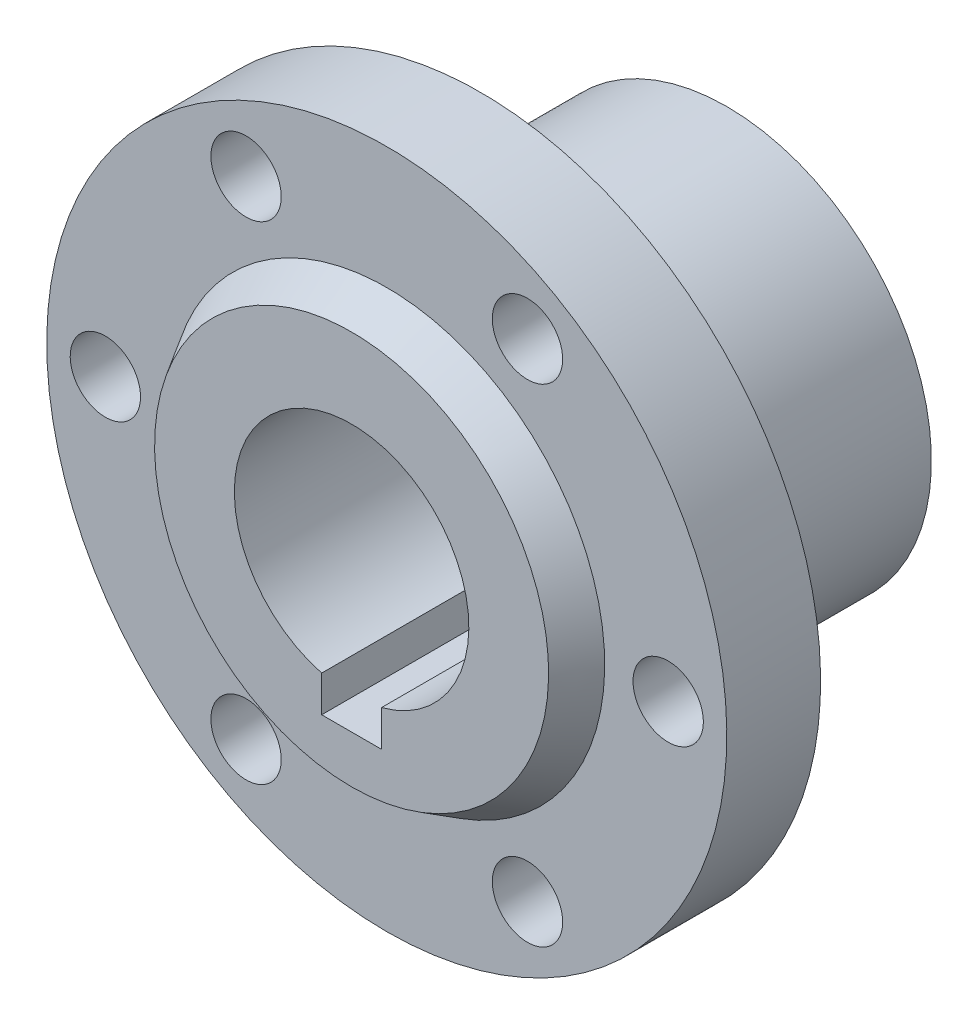
SolidWorks part; units mm, degrees
ref_plane "Front Plane" through (0, 0, 0) normal (0, 0, 1) x (1, 0, 0)
ref_plane "Top Plane" through (0, 0, 0) normal (0, 1, 0) x (1, 0, 0)
ref_plane "Right Plane" through (0, 0, 0) normal (1, 0, 0) x (0, 0, -1)
sketch "Sketch1" plane through (0, 0, 0) normal (1, 0, 0) x (0, 0, -1)
  line L0 (-11, 0) -> (21, 0) construction
  line L1 (21, 0) -> (21, 17.45) construction
  line L2 (21, 17.45) -> (7.03, 17.45)
  line L3 (7.03, 17.45) -> (7.03, 18.5)
  line L4 (7.03, 18.5) -> (0, 18.5)
  line L6 (0, 18.5) -> (0, 29)
  line L8 (0, 29) -> (-8, 29)
  line L9 (-8, 29) -> (-8, 18.5862)
  line L11 (-8, 18.5862) -> (-11, 16.8032)
  line L12 (-11, 16.8032) -> (-11, 0) construction
  line L13 (-11, 10) -> (21, 10)
  line L14 (-11, 10) -> (-11, 16.8032)
  line L15 (21, 10) -> (21, 17.45)
  point P22 (-11, 9.6803)
  dimension "D1" = 10
  dimension "D2" = 29
  dimension "D3" = 18.5
  dimension "D4" = 17.45
  dimension "D5" = 13.97
  dimension "D6" = 6.8032
  dimension "D7" = 8
revolve "Revolve1" add sketch "Sketch1" angle 360 about L0
sketch "Sketch2" plane through (0, 0, 0) normal (0, 0, 1) x (1, 0, 0)
  line L0 (0, 0) -> (0, -12.75) construction
  line L1 (-2.55, -12.75) -> (2.55, -12.75)
  line L2 (-2.55, -12.75) -> (-2.55, -9.6694)
  line L3 (2.55, -12.75) -> (2.55, -9.6694)
  circle A0 centre (0, 0) radius 10 construction
  arc A1 (-2.55, -9.6694) -> (2.55, -9.6694) centre (0, 0) ccw
  point P6 (0, -12.75)
  point P11 (0, -12.8824)
  point P12 (2.55, -12.75)
  dimension "D1" = 12.75
  dimension "D2" = 5.1
extrude "Cut-Extrude1" cut sketch "Sketch2" against normal through all both and the other way through all
sketch "Sketch3" plane through (0, 0, 0) normal (0, 0, -1) x (-1, 0, 0)
  circle A0 centre (0, 0) radius 24 construction
  circle A1 centre (-24, 0) radius 3
  circle A2 centre (0, 0) radius 24 construction
  circle A3 centre (-12, 20.7846) radius 3
  circle A4 centre (0, 0) radius 24 construction
  circle A5 centre (12, 20.7846) radius 3
  circle A6 centre (0, 0) radius 24 construction
  circle A7 centre (24, 0) radius 3
  circle A8 centre (0, 0) radius 24 construction
  circle A9 centre (12, -20.7846) radius 3
  circle A10 centre (0, 0) radius 24 construction
  circle A11 centre (-12, -20.7846) radius 3
  dimension "D1" = 6
  dimension "D3" = 48
  dimension "D2" = 6
extrude "Cut-Extrude2" cut sketch "Sketch3" against normal through all both and the other way through all
